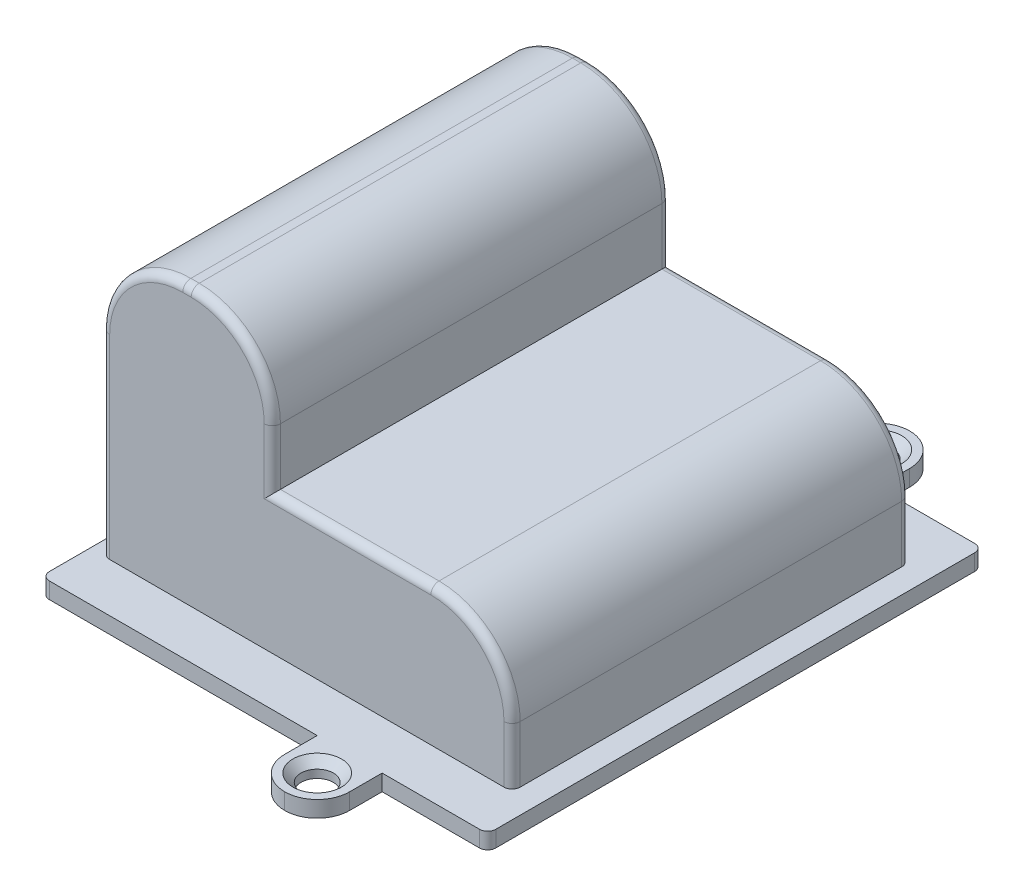
SolidWorks part; units mm, degrees
material "PBT General Purpose"
ref_plane "Front Plane" through (0, 0, 0) normal (0, 0, 1) x (1, 0, 0)
ref_plane "Top Plane" through (0, 0, 0) normal (0, 1, 0) x (1, 0, 0)
ref_plane "Right Plane" through (0, 0, 0) normal (1, 0, 0) x (0, 0, -1)
sketch "Sketch1" plane through (0, 0, 0) normal (0, 0, 1) x (1, 0, 0)
  line L0 (0, 0) -> (55, 0)
  line L1 (55, 0) -> (55, 2)
  line L2 (55, 2) -> (52.0115, 2)
  line L3 (52.0115, 2) -> (52.0115, 19)
  line L4 (52.0115, 19) -> (22.4713, 19)
  line L5 (22.4713, 19) -> (22.4713, 36)
  line L6 (22.4713, 36) -> (1.4368, 36)
  line L7 (1.4368, 36) -> (1.4368, 2)
  line L8 (1.4368, 2) -> (0, 2)
  line L9 (0, 2) -> (0, 0)
  dimension "D1" = 55
  dimension "D2" = 17
  dimension "D3" = 34
  dimension "D4" = 2
  dimension "D5" = 2
extrude "Boss-Extrude1" add sketch "Sketch1" along normal blind 49
fillet "Fillet1" radius 10 3 edges at (52.0115, 19, 24.5) (1.4368, 36, 24.5) (22.4713, 36, 24.5)
fillet "Fillet2" radius 1 16 edges at (11.954, 36, 0) (11.954, 36, 49) (1.4368, 14, 0) (4.3657, 33.0711, 0) (19.5423, 33.0711, 0) (22.4713, 22.5, 0) (32.2414, 19, 0) (49.0826, 16.0711, 0) (52.0115, 5.5, 0) (52.0115, 5.5, 49) (49.0826, 16.0711, 49) (32.2414, 19, 49) (22.4713, 22.5, 49) (19.5423, 33.0711, 49) (4.3657, 33.0711, 49) (1.4368, 14, 49)
sketch "Sketch2" plane through (0, 0, 0) normal (0, -1, 0) x (1, 0, 0)
  line L1 (55, 49) -> (0, 49)
  line L2 (55, 49) -> (55, 55)
  line L3 (55, 55) -> (0, 55)
  line L4 (0, 49) -> (0, 55)
  line L5 (34, 55) -> (42, 55)
  line L6 (34, 55) -> (34, 63)
  line L7 (34, 63) -> (42, 63)
  line L8 (42, 55) -> (42, 63)
  circle A0 centre (38, 59) radius 2
  line M6 (55, 49) -> (0, 49)
  dimension "D5" = 4
  dimension "D1" = 6
  dimension "D2" = 34
  dimension "D3" = 8
  dimension "D4" = 8
extrude "Boss-Extrude2" add sketch "Sketch2" against normal blind 2 contours L4 L2 L3 M6 | L3 L8 L7 L6 A0 region at (27.5, 0, 52) region at (38, 0, 55.1131)
fillet "Fillet3" radius 4 2 edges at (34, 1, 63) (42, 1, 63)
fillet "Fillet4" radius 1 2 edges at (0, 1, 55) (55, 1, 55)
ref_plane "Plane2" through (0, 0, 24.5) normal (0, 0, 1) x (1, 0, 0)
mirror "Mirror7" about plane through (0, 0, 24.5) normal (0, 0, 1) of bodies 102
chamfer "Chamfer1" distance 1 angle 45 2 edges at (38, 2, 57) (38, 2, -8)
